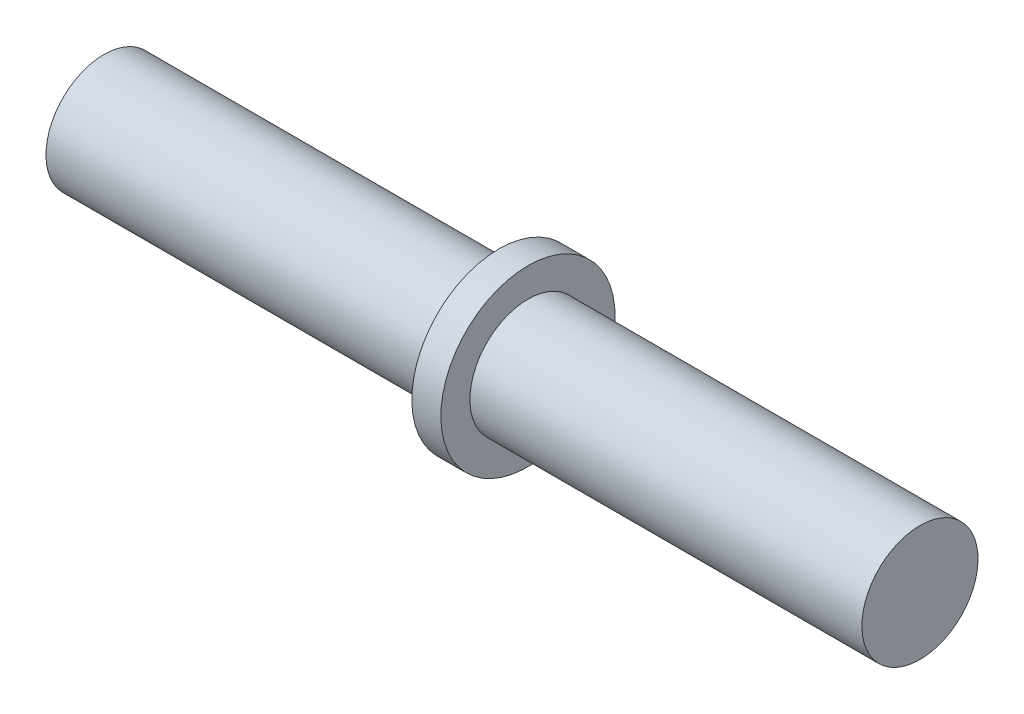
SolidWorks part; units mm, degrees
ref_plane "Front Plane" through (0, 0, 0) normal (0, 0, 1) x (1, 0, 0)
ref_plane "Top Plane" through (0, 0, 0) normal (0, 1, 0) x (1, 0, 0)
ref_plane "Right Plane" through (0, 0, 0) normal (1, 0, 0) x (0, 0, -1)
sketch "Sketch2" plane through (0, 0, 0) normal (0, 0, 1) x (1, 0, 0)
  line L0 (-28.1, 4) -> (-0.9, 4)
  line L1 (-0.9, 4) -> (-0.9, 6)
  line L2 (-0.9, 6) -> (1.1, 6)
  line L3 (1.1, 6) -> (1.1, 4)
  line L4 (1.1, 4) -> (28.1, 4)
  line L6 (28.1, 0) -> (-28.1, 0)
  line L7 (-28.1, 0) -> (-28.1, 4)
  line L8 (28.1, 0) -> (28.1, 4)
  point P2 (0, 0)
  point P6 (18.1, 4)
  point P10 (28.1, 4)
  point P12 (28.1, 4.6494)
  dimension "D1" = 4
  dimension "D2" = 2
  dimension "D3" = 2
  dimension "D5" = 56.2
  dimension "D7" = 27.2
revolve "Revolve1" add sketch "Sketch2" angle 360 about L6
